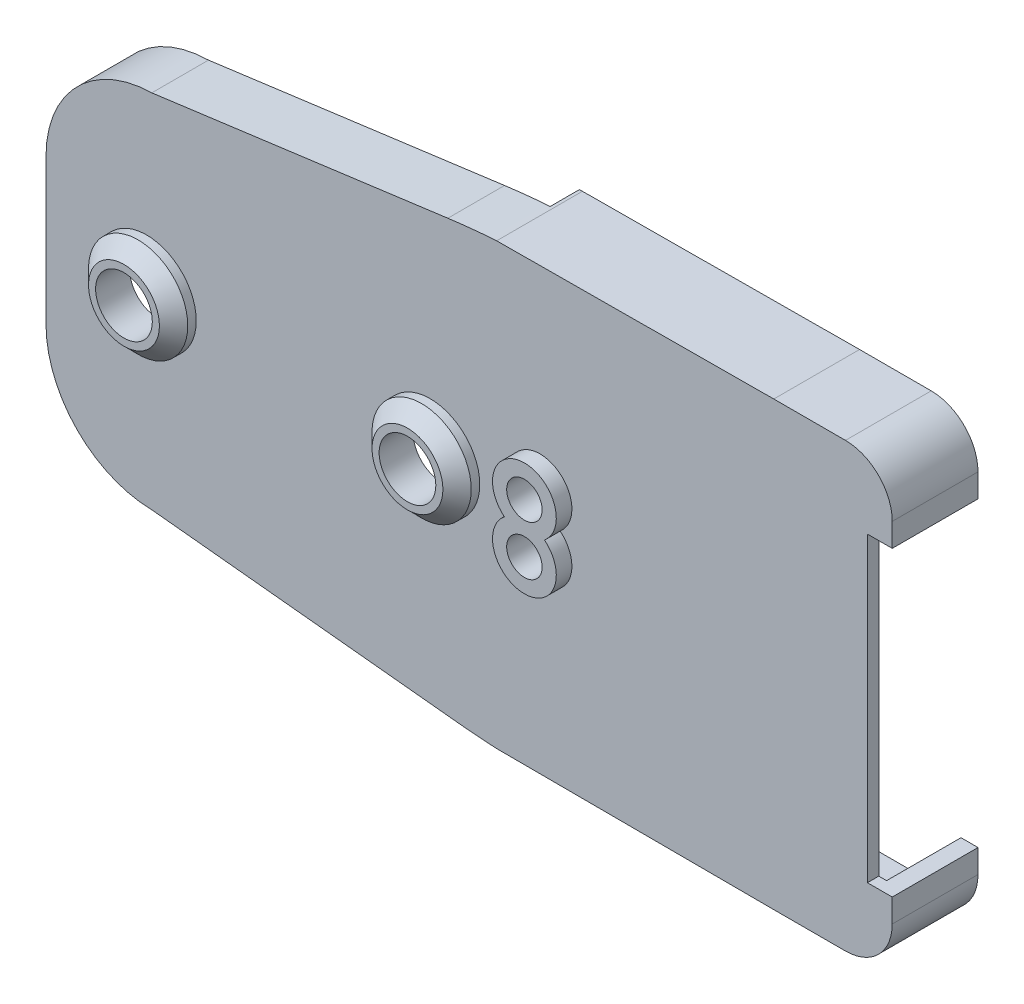
SolidWorks part; units mm, degrees
ref_plane "Front Plane" through (0, 0, 0) normal (0, 0, 1) x (1, 0, 0)
ref_plane "Top Plane" through (0, 0, 0) normal (0, 1, 0) x (1, 0, 0)
ref_plane "Right Plane" through (0, 0, 0) normal (1, 0, 0) x (0, 0, -1)
sketch "Sketch1" plane through (0, 0, 0) normal (0, 0, 1) x (1, 0, 0)
  line L0 (28.25, 25.8898) -> (47.75, 26)
  line L1 (28.25, -1.9348) -> (47.75, -2)
  line L2 (52.75, 12) -> (-2, 12) construction
  line L3 (31.25, 10.25) -> (31.25, 13.75) construction
  line L4 (47.7473, -3.6) -> (52.8, -3.6)
  line L9 (56.1, -0.3) -> (56.1, 1.35)
  line L10 (56.1, 1.35) -> (54.35, 1.35)
  line L11 (54.35, 1.35) -> (54.35, 22.65)
  line L12 (54.35, 22.65) -> (56.1, 22.65)
  line L13 (56.1, 22.65) -> (56.1, 24.3)
  line L14 (52.8, 27.6) -> (47.7455, 27.6)
  line L15 (28.1927, 27.4895) -> (47.7455, 27.6)
  line L16 (54.5, 24.25) -> (54.5, 24.3)
  line L17 (52.8, 26) -> (47.75, 26)
  line L18 (47.75, 26) -> (47.75, 24.25)
  line L19 (47.75, 24.25) -> (28.25, 24.25)
  line L20 (28.25, 24.25) -> (28.25, 25.8898)
  line L21 (24.9613, 25.5616) -> (3.9792, 22.7647)
  line L22 (-2, 16.7647) -> (-2, 6.4853)
  line L23 (3.9792, 0.4853) -> (25.71, -1.7399)
  line L24 (28.25, -1.9348) -> (28.25, -0.25)
  line L25 (28.25, -0.25) -> (47.75, -0.25)
  line L26 (47.75, -0.25) -> (47.75, -2)
  line L27 (47.75, -2) -> (52.8, -2)
  line L28 (54.5, -0.3) -> (54.5, -0.25)
  line L29 (54.5, -0.25) -> (52.75, -0.25)
  line L30 (52.75, -0.25) -> (52.75, 24.25)
  line L31 (52.75, 24.25) -> (54.5, 24.25)
  line L32 (54.5, 24.25) -> (54.5, 24.3)
  line L33 (52.8, 26) -> (47.75, 26)
  line L37 (24.9613, 25.5616) -> (3.9792, 22.7647)
  line L38 (-2, 16.7647) -> (-2, 6.4853)
  line L39 (3.9792, 0.4853) -> (25.71, -1.7399)
  line L43 (47.75, -2) -> (52.8, -2)
  line L44 (54.5, -0.3) -> (54.5, -0.25)
  line L45 (54.5, -0.25) -> (52.75, -0.25)
  line L46 (52.75, -0.25) -> (52.75, 24.25)
  line L47 (52.75, 24.25) -> (54.5, 24.25)
  line L48 (24.7499, 27.1476) -> (3.8642, 24.3635)
  line L49 (-3.6, 16.7647) -> (-3.6, 6.4853)
  line L50 (3.89, -1.1139) -> (25.547, -3.3316)
  line L51 (28.2067, -3.5346) -> (47.7473, -3.6)
  line L52 (27.9684, 27.4743) -> (27.9684, -3.5221)
  line L53 (28.25, -1.9348) -> (28.2067, -3.5346)
  line L54 (26.4684, 27.3474) -> (26.4684, -3.4176)
  line L55 (28.2391, -2.3347) -> (47.7493, -2.4)
  line L56 (47.7493, -2.4) -> (52.8, -2.4)
  line L57 (54.9, -0.3) -> (54.9, 0.15)
  line L58 (54.9, 0.15) -> (53.15, 0.15)
  line L59 (53.15, 0.15) -> (53.15, 23.85)
  line L60 (53.15, 23.85) -> (54.9, 23.85)
  line L61 (54.9, 23.85) -> (54.9, 24.3)
  line L62 (52.8, 26.4) -> (47.7489, 26.4)
  line L63 (28.2356, 26.2897) -> (47.7489, 26.4)
  line L64 (24.9084, 25.9581) -> (3.9515, 23.1645)
  line L65 (-2.4, 16.7647) -> (-2.4, 6.4853)
  line L66 (3.9577, 0.0854) -> (25.6692, -2.1378)
  circle A0 centre (3.5, 12) radius 2
  circle A1 centre (23.5, 12) radius 2
  circle A2 centre (31.25, 13.75) radius 1.25
  circle A3 centre (31.25, 10.25) radius 1.25
  arc A4 (52.8, -3.6) -> (56.1, -0.3) centre (52.8, -0.3) ccw
  arc A5 (56.1, 24.3) -> (52.8, 27.6) centre (52.8, 24.3) ccw
  arc A6 (54.5, 24.3) -> (52.8, 26) centre (52.8, 24.3) ccw
  arc A7 (28.25, 25.8898) -> (24.9613, 25.5616) centre (31.5678, -24) ccw
  arc A8 (3.9792, 22.7647) -> (-2, 16.7647) centre (4, 16.7647) ccw
  arc A9 (-2, 6.4853) -> (3.9792, 0.4853) centre (4, 6.4853) ccw
  arc A10 (25.71, -1.7399) -> (28.25, -1.9348) centre (30.8033, 48) ccw
  arc A11 (52.8, -2) -> (54.5, -0.3) centre (52.8, -0.3) ccw
  arc A12 (54.5, 24.3) -> (52.8, 26) centre (52.8, 24.3) ccw
  arc A13 (28.25, 25.8898) -> (24.9613, 25.5616) centre (31.5678, -24) ccw
  arc A14 (3.9792, 22.7647) -> (-2, 16.7647) centre (4, 16.7647) ccw
  arc A15 (-2, 6.4853) -> (3.9792, 0.4853) centre (4, 6.4853) ccw
  arc A16 (25.71, -1.7399) -> (28.25, -1.9348) centre (30.8033, 48) ccw
  arc A17 (52.8, -2) -> (54.5, -0.3) centre (52.8, -0.3) ccw
  arc A18 (28.1927, 27.4895) -> (24.7499, 27.1476) centre (31.5678, -24) ccw
  arc A19 (3.8642, 24.3635) -> (-3.6, 16.7647) centre (4, 16.7647) ccw
  arc A20 (-3.6, 6.4853) -> (3.89, -1.1139) centre (4, 6.4853) ccw
  arc A21 (25.547, -3.3316) -> (28.2067, -3.5346) centre (30.8033, 48) ccw
  arc A22 (52.8, -2.4) -> (54.9, -0.3) centre (52.8, -0.3) ccw
  arc A23 (54.9, 24.3) -> (52.8, 26.4) centre (52.8, 24.3) ccw
  arc A24 (28.2356, 26.2897) -> (24.9084, 25.9581) centre (31.5678, -24) ccw
  arc A25 (3.9515, 23.1645) -> (-2.4, 16.7647) centre (4, 16.7647) ccw
  arc A26 (-2.4, 6.4853) -> (3.9577, 0.0854) centre (4, 6.4853) ccw
  arc A27 (25.6692, -2.1378) -> (28.2391, -2.3347) centre (30.8033, 48) ccw
  point P28 (31.25, 12)
  dimension "D2" = 2.5
  dimension "D3" = 4
  dimension "D4" = 4
  dimension "D5" = 5.5
  dimension "D6" = 25.5
  dimension "D7" = 33.25
  dimension "D8" = 3.5
  dimension "D10" = 1.5
  dimension "D1" = 0
  dimension "D9" = 1.6
  dimension "D11" = 1.2
extrude "Boss-Extrude1" add sketch "Sketch1" along normal blind 0.8 contours L39 A16 L54 A13 L37 A14 L38 A15 A0 A1 | L54 A16 L52 A13 | L43 A17 L44 L45 L46 L47 L32 A12 L33 L0 A13 L52 A16 L1 A2 A3 | A24 L63 L62 A23 L61 L60 L59 L58 L57 A22 L56 L55 L53 L51 L4 A4 L9 L10 L11 L12 L13 A5 L14 L15 A18 L52 | A24 L52 A18 L54 | A27 L66 A26 L65 A25 L64 A24 L54 A18 L48 A19 L49 A20 L50 A21 | A27 L54 A21 L52 | A27 L52 A21 L53 L55 | L52 A27 L55 L53 A16 | L63 A24 L52 A13 L0 L33 A12 L32 L47 L46 L45 L44 A17 L43 L1 L53 L55 L56 A22 L57 L58 L59 L60 L61 A23 L62 | L54 A27 L52 A16 | L66 A27 L54 A16 L39 A15 L38 A14 L37 A13 A24 L64 A25 L65 A26 | L52 A24 L54 A13 region at (28.0819, 26.2736, 0) region at (38.1057, 25.0977, 0) region at (40.8672, 11.9997, 0) region at (27.2181, 26.0093, 0) region at (27.2195, 11.9696, 0) region at (27.2181, 26.8123, 0) region at (28.3885, 26.8728, 0) region at (28.1065, -2.1261, 0) region at (27.2181, -2.0699, 0) region at (25.7094, 25.6964, 0) region at (13.105, 11.7647, 0) region at (25.6375, 26.4831, 0) region at (28.0959, -2.9153, 0) region at (27.2182, -2.872, 0) region at (38.0617, -1.1088, 0)
extrude "Boss-Extrude2" add sketch "Sketch1<3>" against normal blind 1.7 contours L54 A16 L52 A13 | L54 A27 L52 A16 | L52 A24 L54 A13 region at (27.2181, 26.0093, 0) region at (27.2195, 11.9696, 0) region at (27.2181, -2.0699, 0)
sketch "Sketch1<3>" plane through (0, 0, 0) normal (0, 0, 1) x (1, 0, 0) same geometry as "Sketch1"
extrude "Boss-Extrude5" add sketch "Sketch1<4>" against normal blind 5.25 contours A24 L63 L62 A23 L61 L60 L59 L58 L57 A22 L56 L55 L53 L51 L4 A4 L9 L10 L11 L12 L13 A5 L14 L15 A18 L52 | A24 L52 A18 L54 | A27 L66 A26 L65 A25 L64 A24 L54 A18 L48 A19 L49 A20 L50 A21 | A27 L54 A21 L52 | A27 L52 A21 L53 L55 region at (27.2181, 26.8123, 0) region at (28.3885, 26.8728, 0) region at (25.6375, 26.4831, 0) region at (28.0959, -2.9153, 0) region at (27.2182, -2.872, 0)
sketch "Sketch1<4>" plane through (0, 0, 0) normal (0, 0, 1) x (1, 0, 0) same geometry as "Sketch1"
sketch "Sketch2" plane through (0, 0, -5.25) normal (0, 0, -1) x (-1, 0, 0)
  line L0 (-27.9684, 26.2713) -> (-27.9684, -2.3202) construction
  line L1 (-27.9684, 26.2713) -> (-27.9684, -2.3202)
  line L2 (-27.9684, 26.2713) -> (-27.9684, 27.4743)
  line L3 (-27.9684, -2.3202) -> (-27.9684, -3.5221)
  line L12 (-25.547, -3.3316) -> (-3.89, -1.1139)
  line L13 (3.6, 6.4853) -> (3.6, 16.7647)
  line L14 (-3.8642, 24.3635) -> (-24.7499, 27.1476)
  line L15 (-28.1927, 27.4895) -> (-47.7455, 27.6)
  line L16 (-47.7455, 27.6) -> (-52.8, 27.6)
  line L17 (-56.1, 24.3) -> (-56.1, 22.65)
  line L18 (-56.1, 22.65) -> (-54.35, 22.65)
  line L19 (-54.35, 22.65) -> (-54.35, 1.35)
  line L20 (-54.35, 1.35) -> (-56.1, 1.35)
  line L21 (-56.1, 1.35) -> (-56.1, -0.3)
  line L22 (-52.8, -3.6) -> (-47.7473, -3.6)
  line L23 (-47.7473, -3.6) -> (-28.2067, -3.5346)
  line L24 (-25.547, -3.3316) -> (-3.89, -1.1139)
  line L25 (3.6, 6.4853) -> (3.6, 16.7647)
  line L26 (-3.8642, 24.3635) -> (-24.7499, 27.1476)
  line L27 (-28.1927, 27.4895) -> (-47.7455, 27.6)
  line L28 (-47.7455, 27.6) -> (-52.8, 27.6)
  line L29 (-56.1, 24.3) -> (-56.1, 22.65)
  line L30 (-56.1, 22.65) -> (-54.35, 22.65)
  line L31 (-54.35, 22.65) -> (-54.35, 1.35)
  line L32 (-54.35, 1.35) -> (-56.1, 1.35)
  line L33 (-56.1, 1.35) -> (-56.1, -0.3)
  line L34 (-52.8, -3.6) -> (-47.7473, -3.6)
  line L35 (-47.7473, -3.6) -> (-28.2067, -3.5346)
  arc A6 (-3.89, -1.1139) -> (3.6, 6.4853) centre (-4, 6.4853) ccw
  arc A7 (3.6, 16.7647) -> (-3.8642, 24.3635) centre (-4, 16.7647) ccw
  arc A8 (-24.7499, 27.1476) -> (-28.1927, 27.4895) centre (-31.5678, -24) ccw
  arc A9 (-52.8, 27.6) -> (-56.1, 24.3) centre (-52.8, 24.3) ccw
  arc A10 (-56.1, -0.3) -> (-52.8, -3.6) centre (-52.8, -0.3) ccw
  arc A11 (-28.2067, -3.5346) -> (-25.547, -3.3316) centre (-30.8033, 48) ccw
  arc A12 (-3.89, -1.1139) -> (3.6, 6.4853) centre (-4, 6.4853) ccw
  arc A13 (3.6, 16.7647) -> (-3.8642, 24.3635) centre (-4, 16.7647) ccw
  arc A14 (-24.7499, 27.1476) -> (-28.1927, 27.4895) centre (-31.5678, -24) ccw
  arc A15 (-52.8, 27.6) -> (-56.1, 24.3) centre (-52.8, 24.3) ccw
  arc A16 (-56.1, -0.3) -> (-52.8, -3.6) centre (-52.8, -0.3) ccw
  arc A17 (-28.2067, -3.5346) -> (-25.547, -3.3316) centre (-30.8033, 48) ccw
  line M19 (-25.547, -3.3316) -> (-3.89, -1.1139)
  arc M20 (-3.89, -1.1139) -> (3.6, 6.4853) centre (-4, 6.4853) ccw
  line M21 (3.6, 6.4853) -> (3.6, 16.7647)
  arc M22 (3.6, 16.7647) -> (-3.8642, 24.3635) centre (-4, 16.7647) ccw
  line M23 (-3.8642, 24.3635) -> (-24.7499, 27.1476)
  arc M24 (-24.7499, 27.1476) -> (-28.1927, 27.4895) centre (-31.5678, -24) ccw
  arc M36 (-28.2067, -3.5346) -> (-25.547, -3.3316) centre (-30.8033, 48) ccw
  arc M37 (-28.2356, 26.2897) -> (-24.9084, 25.9581) centre (-31.5678, -24) cw
  line M38 (-24.9084, 25.9581) -> (-3.9515, 23.1645)
  arc M39 (-3.9515, 23.1645) -> (2.4, 16.7647) centre (-4, 16.7647) cw
  line M40 (2.4, 16.7647) -> (2.4, 6.4853)
  arc M41 (2.4, 6.4853) -> (-3.9577, 0.0854) centre (-4, 6.4853) cw
  line M42 (-3.9577, 0.0854) -> (-25.6692, -2.1378)
  arc M43 (-25.6692, -2.1378) -> (-28.2391, -2.3347) centre (-30.8033, 48) cw
  dimension "D1" = 0
extrude "Cut-Extrude1" cut sketch "Sketch2" against normal offset from surface (2.05 mm away) 1.5 contours L3 L2 M43 M36 M19 M20 M21 M22 M23 M24 M37 M38 M39 M40 M41 M42 | L1 M37 M43 M42 M41 M40 M39 M38 region at (13.7531, 11.7834, -5.25) region at (27.526, 26.8728, -5.25) up to face at (27.2182, 11.9698, -1.7)
sketch "Sketch3" plane through (0, 0, -5.25) normal (0, 0, -1) x (-1, 0, 0)
  line L20 (-54.9, 23.85) -> (-54.9, 22.65)
  line L21 (-54.9, 0.15) -> (-54.9, 1.35)
  line L40 (-27.9684, -3.5221) -> (-27.9684, -2.3202)
  line L41 (-28.2391, -2.3347) -> (-47.7493, -2.4)
  line L42 (-47.7493, -2.4) -> (-52.8, -2.4)
  line L43 (-54.9, -0.3) -> (-54.9, 0.15)
  line L44 (-54.9, 0.15) -> (-53.15, 0.15)
  line L45 (-53.15, 0.15) -> (-53.15, 23.85)
  line L46 (-53.15, 23.85) -> (-54.9, 23.85)
  line L47 (-54.9, 23.85) -> (-54.9, 24.3)
  line L48 (-52.8, 26.4) -> (-47.7489, 26.4)
  line L49 (-47.7489, 26.4) -> (-28.2356, 26.2897)
  line L50 (-27.9684, 26.2713) -> (-27.9684, 27.4743)
  line L51 (-28.1927, 27.4895) -> (-47.7455, 27.6)
  line L52 (-47.7455, 27.6) -> (-52.8, 27.6)
  line L53 (-56.1, 24.3) -> (-56.1, 22.65)
  line L54 (-56.1, 22.65) -> (-54.35, 22.65)
  line L55 (-54.35, 22.65) -> (-54.35, 1.35)
  line L56 (-54.35, 1.35) -> (-56.1, 1.35)
  line L57 (-56.1, 1.35) -> (-56.1, -0.3)
  line L58 (-52.8, -3.6) -> (-47.7473, -3.6)
  line L59 (-47.7473, -3.6) -> (-28.2067, -3.5346)
  line L60 (-27.9684, -3.5221) -> (-27.9684, -2.3202)
  line L61 (-28.2391, -2.3347) -> (-47.7493, -2.4)
  line L62 (-47.7493, -2.4) -> (-52.8, -2.4)
  line L63 (-54.9, -0.3) -> (-54.9, 0.15)
  line L64 (-54.9, 0.15) -> (-53.15, 0.15)
  line L65 (-53.15, 0.15) -> (-53.15, 23.85)
  line L66 (-53.15, 23.85) -> (-54.9, 23.85)
  line L67 (-54.9, 23.85) -> (-54.9, 24.3)
  line L68 (-52.8, 26.4) -> (-47.7489, 26.4)
  line L69 (-47.7489, 26.4) -> (-28.2356, 26.2897)
  line L70 (-27.9684, 26.2713) -> (-27.9684, 27.4743)
  line L71 (-28.1927, 27.4895) -> (-47.7455, 27.6)
  line L72 (-47.7455, 27.6) -> (-52.8, 27.6)
  line L73 (-56.1, 24.3) -> (-56.1, 22.65)
  line L74 (-56.1, 22.65) -> (-54.35, 22.65)
  line L75 (-54.35, 22.65) -> (-54.35, 1.35)
  line L76 (-54.35, 1.35) -> (-56.1, 1.35)
  line L77 (-56.1, 1.35) -> (-56.1, -0.3)
  line L78 (-52.8, -3.6) -> (-47.7473, -3.6)
  line L79 (-47.7473, -3.6) -> (-28.2067, -3.5346)
  arc A16 (-28.2067, -3.5346) -> (-27.9684, -3.5221) centre (-30.8033, 48) ccw
  arc A17 (-28.2391, -2.3347) -> (-27.9684, -2.3202) centre (-30.8033, 48) ccw
  arc A18 (-54.9, -0.3) -> (-52.8, -2.4) centre (-52.8, -0.3) ccw
  arc A19 (-52.8, 26.4) -> (-54.9, 24.3) centre (-52.8, 24.3) ccw
  arc A20 (-27.9684, 26.2713) -> (-28.2356, 26.2897) centre (-31.5678, -24) ccw
  arc A21 (-27.9684, 27.4743) -> (-28.1927, 27.4895) centre (-31.5678, -24) ccw
  arc A22 (-52.8, 27.6) -> (-56.1, 24.3) centre (-52.8, 24.3) ccw
  arc A23 (-56.1, -0.3) -> (-52.8, -3.6) centre (-52.8, -0.3) ccw
  arc A24 (-28.2067, -3.5346) -> (-27.9684, -3.5221) centre (-30.8033, 48) ccw
  arc A25 (-28.2391, -2.3347) -> (-27.9684, -2.3202) centre (-30.8033, 48) ccw
  arc A26 (-54.9, -0.3) -> (-52.8, -2.4) centre (-52.8, -0.3) ccw
  arc A27 (-52.8, 26.4) -> (-54.9, 24.3) centre (-52.8, 24.3) ccw
  arc A28 (-27.9684, 26.2713) -> (-28.2356, 26.2897) centre (-31.5678, -24) ccw
  arc A29 (-27.9684, 27.4743) -> (-28.1927, 27.4895) centre (-31.5678, -24) ccw
  arc A30 (-52.8, 27.6) -> (-56.1, 24.3) centre (-52.8, 24.3) ccw
  arc A31 (-56.1, -0.3) -> (-52.8, -3.6) centre (-52.8, -0.3) ccw
  line M36 (-54.9, 0.15) -> (-53.15, 0.15)
  line M37 (-53.15, 0.15) -> (-53.15, 23.85)
  line M38 (-53.15, 23.85) -> (-54.9, 23.85)
  line M50 (-56.1, 22.65) -> (-54.35, 22.65)
  line M51 (-54.35, 22.65) -> (-54.35, 1.35)
  line M52 (-54.35, 1.35) -> (-56.1, 1.35)
  dimension "D1" = 0
extrude "Cut-Extrude2" cut sketch "Sketch3" against normal up to surface (5.25 mm away) contours L21 L20 M36 M37 M38 M50 M51 M52 region at (53.7888, 12, -5.25) up to face at (32.5, 10.25, 0)
sketch "Sketch4" plane through (0, 0, 0.8) normal (0, 0, 1) x (1, 0, 0)
  circle A0 centre (3.5, 12) radius 3.5
  circle A1 centre (23.5, 12) radius 3.5
  circle A2 centre (31.25, 13.75) radius 2.25
  circle A3 centre (31.25, 10.25) radius 2.25
  circle A4 centre (3.5, 12) radius 2 construction
  circle A5 centre (23.5, 12) radius 2 construction
  circle A6 centre (31.25, 13.75) radius 1.25 construction
  circle A7 centre (31.25, 10.25) radius 1.25 construction
  circle A8 centre (31.25, 10.25) radius 1.25
  circle A9 centre (31.25, 13.75) radius 1.25
  circle A10 centre (23.5, 12) radius 2
  circle A11 centre (3.5, 12) radius 2
  circle M24 centre (3.5, 12) radius 2
  circle M25 centre (23.5, 12) radius 2
  circle M26 centre (31.25, 13.75) radius 1.25
  circle M27 centre (31.25, 10.25) radius 1.25
  dimension "D1" = 1.5
  dimension "D2" = 1.5
  dimension "D3" = 1
  dimension "D4" = 1
extrude "Boss-Extrude6" add sketch "Sketch4" along normal blind 1.6 contours A0 M24 | A1 M25 | A3 A2 M26 | A2 A3 M27 | A2 A3 region at (0.099, 12, 0.8) region at (20.099, 12, 0.8) region at (33.226, 12.8063, 0.8) region at (31.25, 12, 0.8) region at (30.4799, 11.5719, 0.8)
chamfer "Chamfer1" distance 1 angle 45 2 edges at (7, 12, 2.4) (27, 12, 2.4)
sketch "Sketch5" plane through (0, 0, 2.4) normal (0, 0, 1) x (1, 0, 0)
  arc A2 (32.6642, 12) -> (29.8358, 12) centre (31.25, 13.75) ccw
  arc A3 (29.8358, 12) -> (32.6642, 12) centre (31.25, 10.25) ccw
  arc A4 (32.6642, 12) -> (29.8358, 12) centre (31.25, 13.75) ccw
  arc A5 (29.8358, 12) -> (32.6642, 12) centre (31.25, 10.25) ccw
  dimension "D1" = 0
extrude "Cut-Extrude3" cut sketch "Sketch5" against normal blind 0.5
